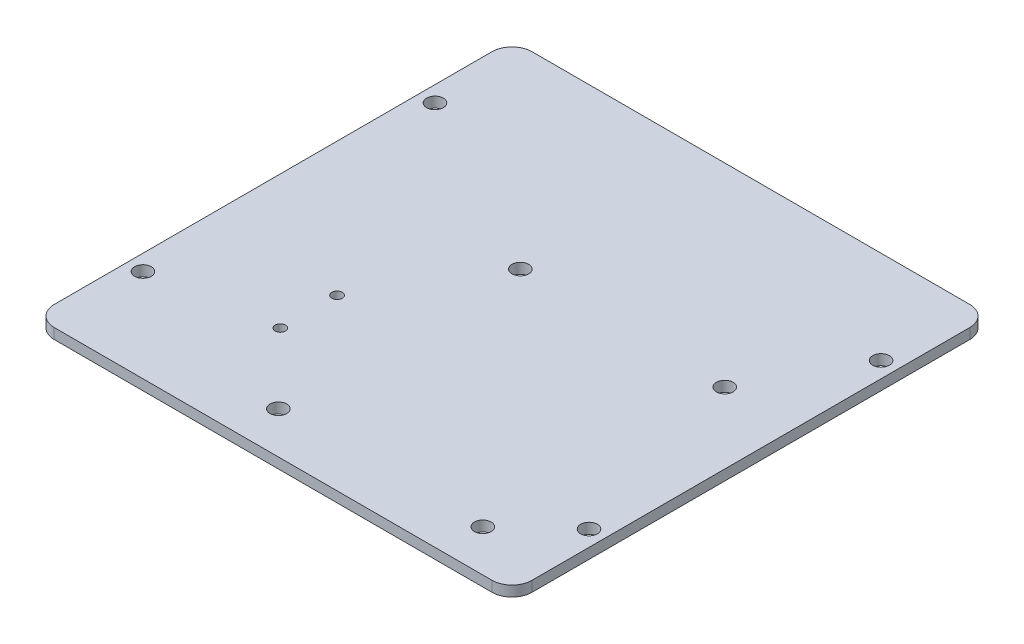
SolidWorks part; units mm, degrees
ref_plane "Plan de face" through (0, 0, 0) normal (0, 0, 1) x (1, 0, 0)
ref_plane "Plan de dessus" through (0, 0, 0) normal (0, 1, 0) x (1, 0, 0)
ref_plane "Plan de droite" through (0, 0, 0) normal (1, 0, 0) x (0, 0, -1)
sketch "Esquisse1" plane through (0, 0, 0) normal (0, 1, 0) x (1, 0, 0)
  line L68 (4.9647, 56.228) -> (-7.0353, 56.228)
  line L69 (51.428, 56.228) -> (4.9647, 56.228)
  line L70 (56.228, -53.4986) -> (56.228, 51.428)
  line L71 (4.9647, -58.2986) -> (51.428, -58.2986)
  line L72 (-7.0353, -58.2986) -> (4.9647, -58.2986)
  line L73 (-53.4986, -58.2986) -> (-7.0353, -58.2986)
  line L74 (-58.2986, 51.428) -> (-58.2986, -53.4986)
  line L75 (-7.0353, 56.228) -> (-53.4986, 56.228)
  line L76 (4.9647, 56.228) -> (-7.0353, 56.228)
  line L77 (51.428, 56.228) -> (4.9647, 56.228)
  line L78 (56.228, -53.4986) -> (56.228, 51.428)
  line L79 (4.9647, -58.2986) -> (51.428, -58.2986)
  line L80 (-7.0353, -58.2986) -> (4.9647, -58.2986)
  line L81 (-53.4986, -58.2986) -> (-7.0353, -58.2986)
  line L82 (-58.2986, 51.428) -> (-58.2986, -53.4986)
  line L83 (-7.0353, 56.228) -> (-53.4986, 56.228)
  arc A39 (56.228, 51.428) -> (51.428, 56.228) centre (51.428, 51.428) ccw
  arc A40 (51.428, -58.2986) -> (56.228, -53.4986) centre (51.428, -53.4986) ccw
  arc A41 (-58.2986, -53.4986) -> (-53.4986, -58.2986) centre (-53.4986, -53.4986) ccw
  arc A42 (-53.4986, 56.228) -> (-58.2986, 51.428) centre (-53.4986, 51.428) ccw
  arc A43 (56.228, 51.428) -> (51.428, 56.228) centre (51.428, 51.428) ccw
  arc A44 (51.428, -58.2986) -> (56.228, -53.4986) centre (51.428, -53.4986) ccw
  arc A45 (-58.2986, -53.4986) -> (-53.4986, -58.2986) centre (-53.4986, -53.4986) ccw
  arc A46 (-53.4986, 56.228) -> (-58.2986, 51.428) centre (-53.4986, 51.428) ccw
  circle A81 centre (-54.4986, -36.0353) radius 2 construction
  circle A82 centre (52.428, -36.0353) radius 2 construction
  circle A84 centre (52.428, 33.9647) radius 2 construction
  circle A85 centre (-54.4986, 33.9647) radius 2 construction
  circle A86 centre (-54.4986, -36.0353) radius 2
  circle A87 centre (52.428, -36.0353) radius 2
  circle A88 centre (52.428, 33.9647) radius 2
  circle A89 centre (-54.4986, 33.9647) radius 2
  dimension "D1" = 0.2
extrude "Boss.-Extru.1" add sketch "Esquisse1" along normal blind 2.5 contours L83 A46 L82 A45 L81 L80 L79 A44 L78 A43 L77 L76 A89 A88 A87 A86 | L76 L83 A46 L82 A45 L81 L80 L79 A44 L78 A43 L77 | A89 | A88 | A87 | A86 region at (-1.0353, 0, 1.0353)
sketch "Esquisse2" [suppressed] plane through (0, 0, 0) normal (0, 1, 0) x (1, 0, 0)
  line L27 (29.4647, -54.4079) -> (29.4647, -58.9079)
  line L28 (38.4647, -58.9079) -> (38.4647, -54.4079)
  line L29 (29.4647, -58.9079) -> (38.4647, -58.9079)
  line L30 (29.4647, -54.4079) -> (29.4647, -58.9079)
  line L31 (38.4647, -58.9079) -> (38.4647, -54.4079)
  line L32 (29.4647, -58.9079) -> (38.4647, -58.9079)
  line L42 (-40.5353, -54.4079) -> (-40.5353, -58.9079)
  line L43 (-31.5353, -58.9079) -> (-31.5353, -54.4079)
  line L44 (-40.5353, -58.9079) -> (-31.5353, -58.9079)
  line L45 (-40.5353, -54.4079) -> (-40.5353, -58.9079)
  line L46 (-31.5353, -58.9079) -> (-31.5353, -54.4079)
  line L47 (-40.5353, -58.9079) -> (-31.5353, -58.9079)
  line L56 (-31.5353, 52.3372) -> (-31.5353, 56.8372)
  line L57 (-40.5353, 56.8372) -> (-40.5353, 52.3372)
  line L58 (-31.5353, 56.8372) -> (-40.5353, 56.8372)
  line L59 (-31.5353, 52.3372) -> (-31.5353, 56.8372)
  line L60 (-40.5353, 56.8372) -> (-40.5353, 52.3372)
  line L61 (-31.5353, 56.8372) -> (-40.5353, 56.8372)
  line L70 (38.4647, 52.3372) -> (38.4647, 56.8372)
  line L71 (29.4647, 56.8372) -> (29.4647, 52.3372)
  line L72 (38.4647, 56.8372) -> (29.4647, 56.8372)
  line L73 (38.4647, 52.3372) -> (38.4647, 56.8372)
  line L74 (29.4647, 56.8372) -> (29.4647, 52.3372)
  line L75 (38.4647, 56.8372) -> (29.4647, 56.8372)
  arc A7 (38.4647, -54.4079) -> (29.4647, -54.4079) centre (33.9647, -54.4079) ccw
  arc A8 (38.4647, -54.4079) -> (29.4647, -54.4079) centre (33.9647, -54.4079) ccw
  arc A11 (-31.5353, -54.4079) -> (-40.5353, -54.4079) centre (-36.0353, -54.4079) ccw
  arc A12 (-31.5353, -54.4079) -> (-40.5353, -54.4079) centre (-36.0353, -54.4079) ccw
  arc A15 (-40.5353, 52.3372) -> (-31.5353, 52.3372) centre (-36.0353, 52.3372) ccw
  arc A16 (-40.5353, 52.3372) -> (-31.5353, 52.3372) centre (-36.0353, 52.3372) ccw
  arc A19 (29.4647, 52.3372) -> (38.4647, 52.3372) centre (33.9647, 52.3372) ccw
  arc A20 (29.4647, 52.3372) -> (38.4647, 52.3372) centre (33.9647, 52.3372) ccw
  dimension "D1" = 0.5
  dimension "D2" = 0.5
  dimension "D3" = 0.5
  dimension "D4" = 0.5
extrude "Enlèv. mat.-Extru.1" [suppressed] cut sketch "Esquisse2" along normal through all contours L73 L75 L74 A20 | L59 L61 L60 A16 | L45 L47 L46 A12 | L30 L32 L31 A8
sketch "Esquisse3" plane through (0, 2.5, 0) normal (0, 1, 0) x (1, 0, 0)
  line L1 (56.228, -53.4986) -> (56.228, 51.428) construction
  line L2 (-53.4986, -58.2986) -> (51.428, -58.2986) construction
  line L3 (39.228, 9.7014) -> (39.228, -48.2986) construction
  circle A0 centre (39.228, 9.7014) radius 2
  circle A1 centre (39.228, -48.2986) radius 2
  circle A2 centre (-9.772, -48.2986) radius 2
  circle A3 centre (-9.772, 9.7014) radius 2
  dimension "D2" = 4
  dimension "D1" = 58
  dimension "D3" = 49
  dimension "D4" = 17
  dimension "D5" = 10
extrude "Trous RPI" cut sketch "Esquisse3" against normal through all
sketch "Esquisse4" [suppressed] plane through (0, 0, 0) normal (0, -1, 0) x (1, 0, 0)
  line L0 (-7.7079, -1.5) -> (-7.7079, 9.5)
  line L1 (-7.7079, 9.5) -> (-15.7079, 9.5)
  line L2 (-15.7079, 9.5) -> (-15.7079, 27.5)
  line L3 (-15.7079, 27.5) -> (-20.7079, 27.5)
  line L20 (-20.7079, 27.5) -> (-20.7079, -22.5)
  line L21 (-20.7079, -22.5) -> (-15.7079, -22.5)
  line L22 (-15.7079, -22.5) -> (-15.7079, -8.5)
  line L23 (-15.7079, -8.5) -> (-7.7079, -8.5)
  line L24 (-7.7079, -8.5) -> (-7.7079, -2.5)
  line L29 (-9.2079, 28) -> (-9.2079, -28) construction
  line L30 (-58.2079, -51.3372) -> (-58.2079, 53.4079) construction
  line L76 (-40.7079, -22.5) -> (-40.7079, 27.5)
  line L77 (-40.7079, 27.5) -> (-45.7079, 27.5)
  line L78 (-45.7079, 27.5) -> (-45.7079, -22.5)
  line L79 (-45.7079, -22.5) -> (-40.7079, -22.5)
  line L80 (38.4647, 58.2079) -> (51.3372, 58.2079) construction
  line L81 (-7.7079, -1.5) -> (-7.7079, -2.5)
  line L82 (-15.7079, -1.5) -> (-7.7079, -1.5) construction
  line L83 (-7.7079, -2.5) -> (-15.7079, -2.5) construction
  line L84 (17.4647, 58.2079) -> (17.4647, 55.2079)
  line L85 (-31.5353, 58.2079) -> (29.4647, 58.2079) construction
  line L86 (20.4647, 52.2079) -> (24.4647, 52.2079)
  line L87 (56.1372, 53.4079) -> (56.1372, -51.3372) construction
  line L88 (27.4647, 55.2079) -> (27.4647, 58.2079)
  line L89 (17.4647, 58.2079) -> (27.4647, 58.2079)
  line L90 (29.4647, 54.4079) -> (29.4647, 58.2079) construction
  line L112 (7.6372, 25.2079) -> (46.6372, 25.2079) construction
  line L129 (4.6372, 28.2079) -> (7.6372, 28.2079)
  line L130 (4.6372, 28.2079) -> (4.6372, 22.2079)
  line L131 (4.6372, 22.2079) -> (7.6372, 22.2079)
  line L132 (7.6372, 28.2079) -> (7.6372, 22.2079)
  line L133 (46.6372, 28.2079) -> (49.6372, 28.2079)
  line L134 (46.6372, 28.2079) -> (46.6372, 22.2079)
  line L135 (46.6372, 22.2079) -> (49.6372, 22.2079)
  line L136 (49.6372, 28.2079) -> (49.6372, 22.2079)
  line L137 (4.6372, -1.7921) -> (7.6372, -1.7921)
  line L138 (4.6372, -1.7921) -> (4.6372, 4.2079)
  line L139 (4.6372, 4.2079) -> (7.6372, 4.2079)
  line L140 (7.6372, -1.7921) -> (7.6372, 4.2079)
  line L141 (49.6372, -1.7921) -> (46.6372, -1.7921)
  line L142 (49.6372, -1.7921) -> (49.6372, 4.2079)
  line L143 (49.6372, 4.2079) -> (46.6372, 4.2079)
  line L144 (46.6372, -1.7921) -> (46.6372, 4.2079)
  line L383 (-9.2079, 0) -> (-9.2079, 8) construction
  line L384 (-9.2079, 8) -> (-17.2079, 8) construction
  line L385 (-17.2079, 8) -> (-17.2079, 26) construction
  line L386 (-17.2079, 26) -> (-19.2079, 26) construction
  line L387 (-19.2079, 26) -> (-19.2079, -21) construction
  line L388 (-19.2079, -21) -> (-17.2079, -21) construction
  line L389 (-17.2079, -21) -> (-17.2079, -7) construction
  line L390 (-17.2079, -7) -> (-9.2079, -7) construction
  line L391 (-9.2079, -7) -> (-9.2079, -4) construction
  line L392 (-9.2079, -4) -> (-17.2079, -4) construction
  line L393 (-17.2079, -4) -> (-17.2079, 0) construction
  line L394 (-17.2079, 0) -> (-9.2079, 0) construction
  line L395 (-42.2079, -21) -> (-42.2079, 26) construction
  line L396 (-42.2079, 26) -> (-44.2079, 26) construction
  line L397 (-44.2079, 26) -> (-44.2079, -21) construction
  line L398 (-44.2079, -21) -> (-42.2079, -21) construction
  line L399 (-9.2079, 0) -> (-9.2079, 8)
  line L400 (-9.2079, 8) -> (-17.2079, 8)
  line L401 (-17.2079, 8) -> (-17.2079, 26)
  line L402 (-17.2079, 26) -> (-19.2079, 26)
  line L403 (-19.2079, 26) -> (-19.2079, -21)
  line L404 (-19.2079, -21) -> (-17.2079, -21)
  line L405 (-17.2079, -21) -> (-17.2079, -7)
  line L406 (-17.2079, -7) -> (-9.2079, -7)
  line L407 (-9.2079, -7) -> (-9.2079, -4)
  line L408 (-9.2079, -4) -> (-17.2079, -4)
  line L409 (-17.2079, -4) -> (-17.2079, 0)
  line L410 (-17.2079, 0) -> (-9.2079, 0)
  line L411 (-42.2079, -21) -> (-42.2079, 26)
  line L412 (-42.2079, 26) -> (-44.2079, 26)
  line L413 (-44.2079, 26) -> (-44.2079, -21)
  line L414 (-44.2079, -21) -> (-42.2079, -21)
  line L415 (-15.7079, -2.5) -> (-15.7079, -1.5) construction
  circle A3 centre (-45.2079, -28) radius 1.25
  circle A5 centre (-9.2079, 28) radius 1.25
  circle A7 centre (-9.2079, -28) radius 1.25
  arc A9 (17.4647, 55.2079) -> (20.4647, 52.2079) centre (20.4647, 55.2079) ccw
  arc A10 (24.4647, 52.2079) -> (27.4647, 55.2079) centre (24.4647, 55.2079) ccw
  point P1 (-9.2079, 0)
  point P57 (48.1372, 22.2079)
  point P59 (22.4647, 58.2079)
  point P61 (22.4647, 52.2079)
  dimension "D12" = 2.5
  dimension "D5" = 3
  dimension "D6" = 45
  dimension "D7" = 30
  dimension "D8" = 6.5
  dimension "D9" = 30
  dimension "D10" = 6
  dimension "D11" = 6
  dimension "D13" = 3
  dimension "D14" = 2
  dimension "D2" = 56
  dimension "D3" = 36
  dimension "D4" = 13
  dimension "10" = 10
  dimension "D15" = 1.5
extrude "Enlèv. mat.-Extru.2" [suppressed] cut sketch "Esquisse4" against normal through all contours L130 L129 L132 L131 | L134 L133 L136 L135 | L142 L141 L144 L143 | L138 L137 L140 L139 | A5 | A3 | A7 | L0 L1 L2 L3 L20 L21 L22 L23 L24 L81 | L76 L77 L78 L79
sketch "Esquisse5" plane through (0, 0, 0) normal (0, -1, 0) x (-1, 0, 0)
  line L1 (58.2986, 51.428) -> (58.2986, -53.4986) construction
  line L2 (53.4986, -58.2986) -> (-51.428, -58.2986) construction
  circle A0 centre (26.2986, -31.2986) radius 1.25
  circle A1 centre (26.2986, -17.6986) radius 1.25
  dimension "D2" = 2.5
  dimension "D4" = 32
  dimension "D1" = 13.6
  dimension "D3" = 27
extrude "Trous ICM" cut sketch "Esquisse5" against normal through all
